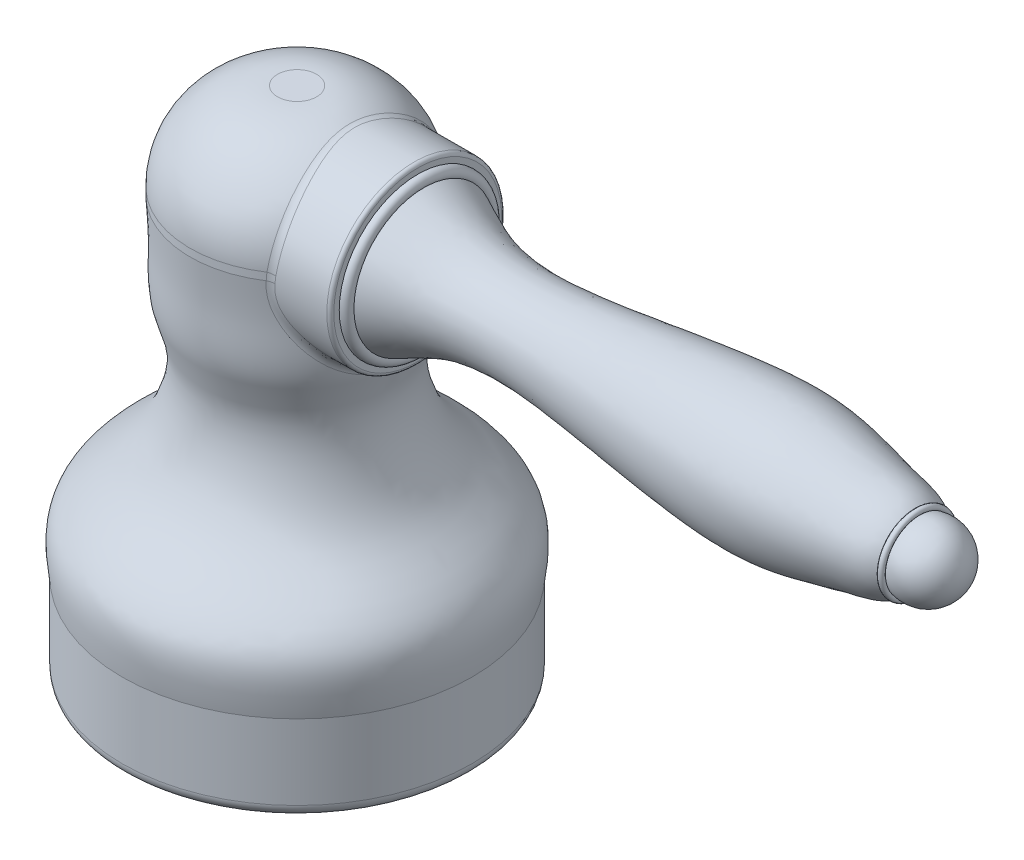
SolidWorks part; units mm, degrees
ref_plane "Front" through (0, 0, 0) normal (0, 0, 1) x (1, 0, 0)
ref_plane "Top" through (0, 0, 0) normal (0, 1, 0) x (1, 0, 0)
ref_plane "Right" through (0, 0, 0) normal (1, 0, 0) x (0, 0, -1)
other "Configuration Table"
sketch "Sketch1" plane through (0, 0, 0) normal (0, 0, 1) x (1, 0, 0)
  line L0 (-0.3774, -0.2779) -> (13.6226, -0.2779)
  line L1 (13.6226, -0.2779) -> (13.6226, 6.7221)
  line L2 (8.1874, 33.1213) -> (8.1874, 40.7221)
  line L3 (8.1874, 40.7221) -> (-0.3774, 40.7221)
  line L4 (-0.3774, -0.2779) -> (-0.3774, 40.7221) construction
  line L5 (-0.3774, -0.2779) -> (-0.3774, 40.7221)
  spline S0 degree 3 poles (13.6226, 6.7221) (13.8119, 8.0804) (14.3165, 11.7009) (9.466, 14.4336) (7.2758, 18.7999) (6.6217, 22.6812) (8.2046, 26.2005) (7.9514, 29.641) (8.1136, 32.0337) (8.1874, 33.1213) knots 0 0 0 0 0.134304 0.357958 0.491853 0.646238 0.748133 0.885515 1 1 1 1
  dimension "D1" = 14
  dimension "D2" = 41
  dimension "D3" = 7
revolve "Revolve1" add sketch "Sketch1" angle 360 about L4
sketch "Sketch2" plane through (0, 0, 0) normal (0, 0, 1) x (1, 0, 0)
  line L0 (0, 33.1213) -> (52.9522, 33.1213) construction
  line L1 (9.2774, 39.4047) -> (9.2774, 39.8405)
  line L2 (8.9966, 40.1213) -> (0, 40.1213)
  line L3 (0, 40.1213) -> (0, 33.1213)
  line L4 (0, 33.1213) -> (52.9522, 33.1213)
  arc A0 (9.7653, 38.7163) -> (9.2774, 39.4047) centre (9.3244, 38.9208) ccw
  arc A1 (49.4555, 35.8717) -> (49.0489, 36.1164) centre (49.2522, 35.994) ccw
  arc A2 (52.9522, 33.1213) -> (49.4555, 35.8717) centre (50.1222, 33.1213) ccw
  arc A3 (9.2774, 39.8405) -> (8.9966, 40.1213) centre (8.9966, 39.8405) ccw
  spline S0 degree 3 poles (49.0489, 36.1164) (48.2461, 36.6753) (45.3784, 37.1582) (40.286, 38.5207) (33.3908, 38.3062) (23.838, 36.9015) (14.9903, 36.0676) (11.3162, 37.998) (9.7653, 38.7163) knots 0.014865 0.014865 0.014865 0.014865 0.089809 0.239761 0.378677 0.601257 0.835911 0.988401 0.988401 0.988401 0.988401
  dimension "D1" = 7
revolve "Revolve2" add sketch "Sketch2" angle 360 about L0
fillet "Fillet3" radius 7 1 edges at (8.1874, 40.7221, 0)
fillet "Fillet4" radius 1 4 edges at (7.8915, 26.1299, 0.3468) (4.0784, 40.0359, 1.0897)
fillet "Fillet5" radius 1 1 edges at (13.6226, -0.2779, 0)
